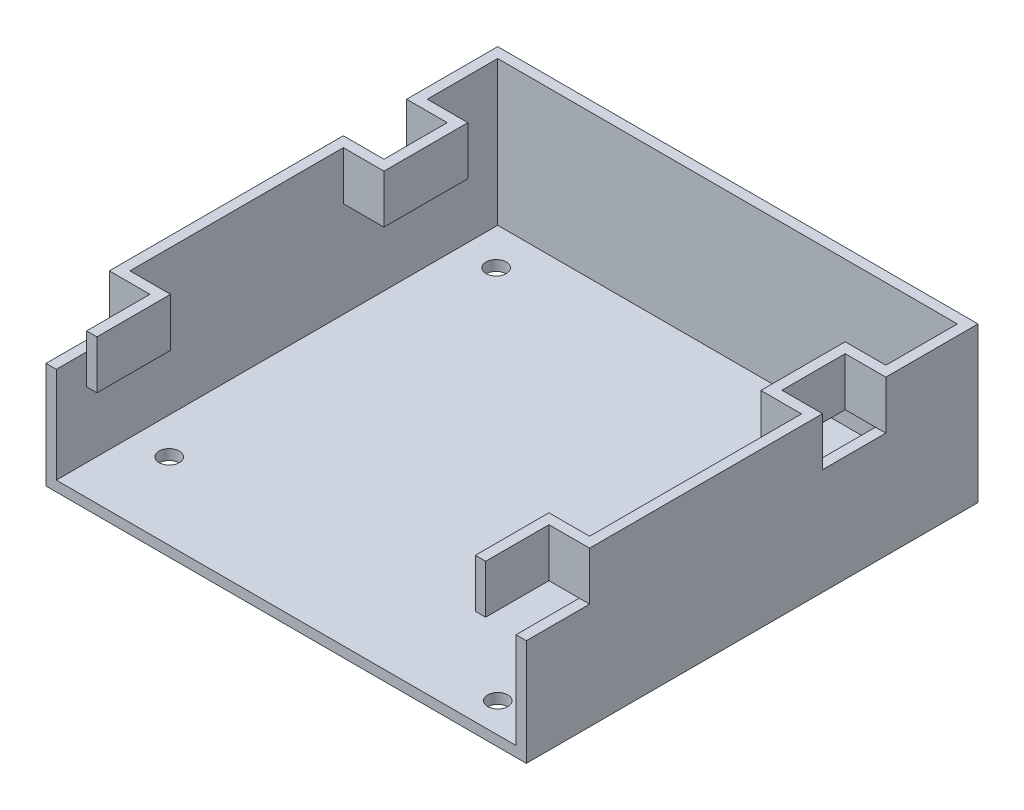
SolidWorks part; units mm, degrees
ref_plane "Front Plane" through (0, 0, 0) normal (0, 0, 1) x (1, 0, 0)
ref_plane "Top Plane" through (0, 0, 0) normal (0, 1, 0) x (1, 0, 0)
ref_plane "Right Plane" through (0, 0, 0) normal (1, 0, 0) x (0, 0, -1)
sketch "Sketch1" plane through (0, 0, 0) normal (0, 1, 0) x (1, 0, 0)
  line L1 (0, 0) -> (89.12, 0)
  line L2 (0, 0) -> (0, 85.57)
  line L3 (0, 85.57) -> (89.12, 85.57)
  line L4 (89.12, 0) -> (89.12, 85.57)
  dimension "D1" = 89.12
  dimension "D2" = 85.57
extrude "Boss-Extrude1" add sketch "Sketch1" along normal blind 2
sketch "Sketch3" plane through (0, 0, 0) normal (0, 0, 1) x (1, 0, 0)
  line L1 (0, 0) -> (-2, 0)
  line L2 (0, 0) -> (0, 30)
  line L3 (0, 30) -> (-2, 30)
  line L4 (-2, 0) -> (-2, 30)
  dimension "D1" = 2
  dimension "D2" = 30
extrude "Boss-Extrude2" add sketch "Sketch3" against normal blind 85.57
sketch "Sketch4" plane through (0, 0, 0) normal (0, 0, 1) x (1, 0, 0)
  line L1 (89.12, 0) -> (91.12, 0)
  line L2 (89.12, 0) -> (89.12, 30)
  line L3 (89.12, 30) -> (91.12, 30)
  line L4 (91.12, 0) -> (91.12, 30)
  dimension "D1" = 30
  dimension "D2" = 2
extrude "Boss-Extrude3" add sketch "Sketch4" against normal blind 85.57
sketch "Sketch5" plane through (0, 0, 0) normal (0, 1, 0) x (1, 0, 0)
  line L1 (-2, 85.57) -> (91.12, 85.57)
  line L2 (-2, 85.57) -> (-2, 87.57)
  line L3 (-2, 87.57) -> (91.12, 87.57)
  line L4 (91.12, 85.57) -> (91.12, 87.57)
  dimension "D1" = 2
extrude "Boss-Extrude4" add sketch "Sketch5" along normal blind 30
sketch "Sketch6" plane through (0, 0, 0) normal (0, 1, 0) x (1, 0, 0)
  line L0 (89.12, 0) -> (89.12, 5.755) construction
  line L1 (89.12, 0) -> (89.12, 85.57) construction
  line L2 (89.12, 5.755) -> (79.835, 5.755) construction
  line L3 (79.835, 5.755) -> (79.835, 0) construction
  line L4 (0, 0) -> (89.12, 0) construction
  circle A0 centre (79.835, 5.755) radius 1.96
  dimension "D3" = 3.92
extrude "Cut-Extrude2" cut sketch "Sketch6" along normal blind 30
sketch "Sketch7" plane through (0, 2, 0) normal (0, 1, 0) x (1, 0, 0)
  line L0 (89.12, 85.57) -> (82.285, 85.57) construction
  line L1 (0, 85.57) -> (89.12, 85.57) construction
  line L2 (82.285, 85.57) -> (82.285, 76.225) construction
  line L3 (82.285, 76.225) -> (89.12, 76.225) construction
  line L4 (89.12, 0) -> (89.12, 85.57) construction
  circle A0 centre (82.285, 76.225) radius 1.96
  dimension "D3" = 3.92
  dimension "D1" = 6.835
extrude "Cut-Extrude3" cut sketch "Sketch7" against normal blind 30
sketch "Sketch8" plane through (0, 0, 0) normal (0, 1, 0) x (1, 0, 0)
  line L0 (0, 85.57) -> (6.985, 85.57) construction
  line L1 (0, 85.57) -> (89.12, 85.57) construction
  line L2 (6.985, 85.57) -> (6.985, 78.28) construction
  line L3 (6.985, 78.28) -> (0, 78.28) construction
  line L4 (0, 85.57) -> (0, 0) construction
  circle A0 centre (6.985, 78.28) radius 1.96
  dimension "D3" = 3.92
extrude "Cut-Extrude4" cut sketch "Sketch8" along normal blind 30
sketch "Sketch9" plane through (0, 2, 0) normal (0, 1, 0) x (1, 0, 0)
  line L0 (0, 0) -> (0, 14.85) construction
  line L1 (0, 85.57) -> (0, 0) construction
  line L2 (0, 14.85) -> (7.035, 14.85) construction
  line L3 (7.035, 14.85) -> (7.035, 0) construction
  line L4 (0, 0) -> (89.12, 0) construction
  circle A0 centre (7.035, 14.85) radius 1.96
  dimension "D3" = 3.92
  dimension "D1" = 14.85
extrude "Cut-Extrude5" cut sketch "Sketch9" against normal blind 30
sketch "Sketch10" plane through (89.12, 0, 0) normal (-1, 0, 0) x (0, 0, 1)
  line L0 (0, 2) -> (0, 20.6) construction
  line L1 (0, 30) -> (0, 2) construction
  line L2 (0, 20.6) -> (-32.6241, 20.6) construction
  line L3 (-32.6241, 20.6) -> (-32.6241, 2) construction
  line L4 (0, 2) -> (-85.57, 2) construction
  line L5 (-32.6241, 20.6) -> (-32.6241, 30) construction
  line L6 (-85.57, 30) -> (0, 30) construction
  dimension "D1" = 18.6
sketch "Sketch11" plane through (0, 30, 0) normal (0, 1, 0) x (1, 0, 0)
  line L1 (89.12, 0) -> (83.24, 0)
  line L2 (89.12, 0) -> (89.12, 12.27)
  line L3 (89.12, 12.27) -> (83.24, 12.27)
  line L4 (83.24, 0) -> (83.24, 12.27)
  line L5 (83.24, 0) -> (81.24, 0)
  line L6 (83.24, 0) -> (83.24, 12.27)
  line L7 (83.24, 12.27) -> (81.24, 12.27)
  line L8 (81.24, 0) -> (81.24, 12.27)
  line L9 (81.24, 12.27) -> (89.12, 12.27)
  line L10 (81.24, 12.27) -> (81.24, 14.27)
  line L11 (81.24, 14.27) -> (89.12, 14.27)
  line L12 (89.12, 12.27) -> (89.12, 14.27)
  line M8 (89.12, 85.57) -> (89.12, 0)
  dimension "D1" = 5.88
  dimension "D2" = 12.27
  dimension "D3" = 2
  dimension "D4" = 2
extrude "Boss-Extrude5" add sketch "Sketch11" against normal blind 9.4 contours L11 L10 L7 L3 M8 | L8 L5 L4 L7 region at (82.24, 30, -6.135) region at (85.18, 30, -13.27)
sketch "Sketch12" plane through (0, 30, 0) normal (0, 1, 0) x (1, 0, 0)
  line L1 (89.12, 12.27) -> (91.12, 12.27)
  line L2 (89.12, 12.27) -> (89.12, 0)
  line L3 (89.12, 0) -> (91.12, 0)
  line L4 (91.12, 12.27) -> (91.12, 0)
extrude "Cut-Extrude6" cut sketch "Sketch12" against normal blind 9.4
sketch "Sketch13" plane through (0, 30, 0) normal (0, 1, 0) x (1, 0, 0)
  line L0 (89.12, 85.57) -> (89.12, 57.43) construction
  line L1 (89.12, 85.57) -> (89.12, 14.27) construction
  line L3 (89.12, 57.43) -> (83.24, 57.43)
  line L4 (89.12, 57.43) -> (89.12, 69.7)
  line L5 (89.12, 69.7) -> (83.24, 69.7)
  line L6 (83.24, 57.43) -> (83.24, 69.7)
  line L7 (83.24, 69.7) -> (81.24, 69.7)
  line L8 (83.24, 69.7) -> (83.24, 57.43)
  line L9 (83.24, 57.43) -> (81.24, 57.43)
  line L10 (81.24, 69.7) -> (81.24, 57.43)
  line L11 (81.24, 57.43) -> (89.12, 57.43)
  line L12 (81.24, 57.43) -> (81.24, 55.3598)
  line L13 (81.24, 55.3598) -> (89.12, 55.3598)
  line L14 (89.12, 57.43) -> (89.12, 55.3598)
  line L15 (81.24, 69.7) -> (89.12, 69.7)
  line L16 (81.24, 69.7) -> (81.24, 71.7)
  line L17 (81.24, 71.7) -> (89.12, 71.7)
  line L18 (89.12, 69.7) -> (89.12, 71.7)
  line M25 (89.12, 85.57) -> (89.12, 14.27)
  dimension "D1" = 28.14
  dimension "D2" = 12.27
  dimension "D3" = 5.88
  dimension "D4" = 2
  dimension "D5" = 2.0702
  dimension "D6" = 2
extrude "Boss-Extrude6" add sketch "Sketch13" against normal blind 9.4 contours L17 L16 L7 L5 M25 | L7 L10 L9 L6 | L12 L13 L3 L9 M25 region at (85.18, 30, -56.3949) region at (82.24, 30, -63.565) region at (85.18, 30, -70.7)
sketch "Sketch14" plane through (0, 30, 0) normal (0, 1, 0) x (1, 0, 0)
  line L0 (91.12, 87.57) -> (91.12, 12.27) construction
  line L1 (89.12, 69.7) -> (91.12, 69.7)
  line L2 (89.12, 69.7) -> (89.12, 57.43)
  line L3 (89.12, 57.43) -> (91.12, 57.43)
  line L4 (91.12, 69.7) -> (91.12, 57.43)
extrude "Cut-Extrude7" cut sketch "Sketch14" against normal blind 9.4
sketch "Sketch15" plane through (0, 30, 0) normal (0, 1, 0) x (1, 0, 0)
  line L0 (0, 85.57) -> (0, 57.64) construction
  line L1 (0, 85.57) -> (0, 0) construction
  line L3 (0, 57.64) -> (5.88, 57.64)
  line L4 (0, 57.64) -> (0, 69.91)
  line L5 (0, 69.91) -> (5.88, 69.91)
  line L6 (5.88, 57.64) -> (5.88, 69.91)
  line L7 (5.88, 69.91) -> (7.88, 69.91)
  line L8 (5.88, 69.91) -> (5.88, 57.64)
  line L9 (5.88, 57.64) -> (7.88, 57.64)
  line L10 (7.88, 69.91) -> (7.88, 57.64)
  line L11 (0, 57.64) -> (7.88, 57.64)
  line L12 (0, 57.64) -> (0, 55.64)
  line L13 (0, 55.64) -> (7.88, 55.64)
  line L14 (7.88, 57.64) -> (7.88, 55.64)
  line L15 (0, 69.91) -> (7.88, 69.91)
  line L16 (0, 69.91) -> (0, 71.91)
  line L17 (0, 71.91) -> (7.88, 71.91)
  line L18 (7.88, 69.91) -> (7.88, 71.91)
  line M12 (0, 0) -> (0, 85.57)
  dimension "D1" = 27.93
  dimension "D2" = 5.88
  dimension "D3" = 12.27
  dimension "D4" = 2
  dimension "D5" = 2
  dimension "D6" = 2
extrude "Boss-Extrude7" add sketch "Sketch15" against normal blind 9.4 contours L7 L18 L17 L5 M12 | L10 L7 L6 L9 | L14 L9 L3 L13 M12 region at (3.94, 30, -56.64) region at (6.88, 30, -63.775) region at (3.94, 30, -70.91)
sketch "Sketch16" plane through (0, 30, 0) normal (0, 1, 0) x (1, 0, 0)
  line L0 (-2, 87.57) -> (-2, 0) construction
  line L1 (-2, 69.91) -> (0, 69.91)
  line L2 (-2, 69.91) -> (-2, 57.64)
  line L3 (-2, 57.64) -> (0, 57.64)
  line L4 (0, 69.91) -> (0, 57.64)
extrude "Cut-Extrude8" cut sketch "Sketch16" against normal blind 9.4
sketch "Sketch17" plane through (0, 30, 0) normal (0, 1, 0) x (1, 0, 0)
  line L0 (0, 0) -> (89.12, 0) construction
  line L1 (0, 0) -> (5.88, 0)
  line L2 (0, 0) -> (0, 12.27)
  line L3 (0, 12.27) -> (5.88, 12.27)
  line L4 (5.88, 0) -> (5.88, 12.27)
  line L5 (5.88, 12.27) -> (7.88, 12.27)
  line L6 (5.88, 12.27) -> (5.88, 0)
  line L7 (5.88, 0) -> (7.88, 0)
  line L8 (7.88, 12.27) -> (7.88, 0)
  line L9 (0, 55.64) -> (0, 0) construction
  line L10 (7.88, 12.27) -> (0, 12.27)
  line L11 (7.88, 12.27) -> (7.88, 14.27)
  line L12 (7.88, 14.27) -> (0, 14.27)
  line L13 (0, 12.27) -> (0, 14.27)
  line M13 (0, 0) -> (0, 55.64)
  dimension "D1" = 12.27
  dimension "D2" = 5.88
  dimension "D3" = 2
  dimension "D4" = 2
extrude "Boss-Extrude8" add sketch "Sketch17" against normal blind 9.4 contours L11 L12 L3 L5 M13 | L8 L5 L4 L7 region at (6.88, 30, -6.135) region at (3.94, 30, -13.27)
sketch "Sketch18" plane through (0, 30, 0) normal (0, 1, 0) x (1, 0, 0)
  line L0 (-2, 57.64) -> (-2, 0) construction
  line L1 (0, 0) -> (-2, 0)
  line L2 (0, 0) -> (0, 12.27)
  line L3 (0, 12.27) -> (-2, 12.27)
  line L4 (-2, 0) -> (-2, 12.27)
extrude "Cut-Extrude9" cut sketch "Sketch18" against normal blind 9.4
equation "\"tol1\"= 0.1cm"
equation "\"D1@Sketch1\"=8.812cm +\"tol1\""
equation "\"D2@Sketch1\"=8.457cm +\"tol1\""
equation "\"D1@Boss-Extrude2\"=8.457 +\"tol1\""
equation "\"D1@Boss-Extrude3\"=8.457 +\"tol1\""
equation "\"D1@Sketch6\"=0.5255 + \"tol2\""
equation "\"hole\"= 0.392cm"
equation "\"D3@Sketch6\"=\"hole\""
equation "\"tol2\"= \"tol1\" / 2"
equation "\"D2@Sketch6\"=0.8785 + \"tol2\""
equation "\"D2@Sketch9\"=0.6535 + \"tol2\""
equation "\"D3@Sketch9\"=\"hole\""
equation "\"D1@Sketch9\"=1.435 + \"tol2\""
equation "\"D2@Sketch8\"=0.6485 + \"tol2\""
equation "\"D1@Sketch8\"=0.679 + \"tol2\""
equation "\"D3@Sketch8\"=\"hole\""
equation "\"D3@Sketch7\"=\"hole\""
equation "\"D2@Sketch7\"=0.8845 + \"tol2\""
equation "\"D1@Sketch7\"=0.6335 + \"tol2\""
equation "\"heightTol\"= 0.5cm"
equation "\"D1@Sketch10\"=1.36 + \"heightTol\""
